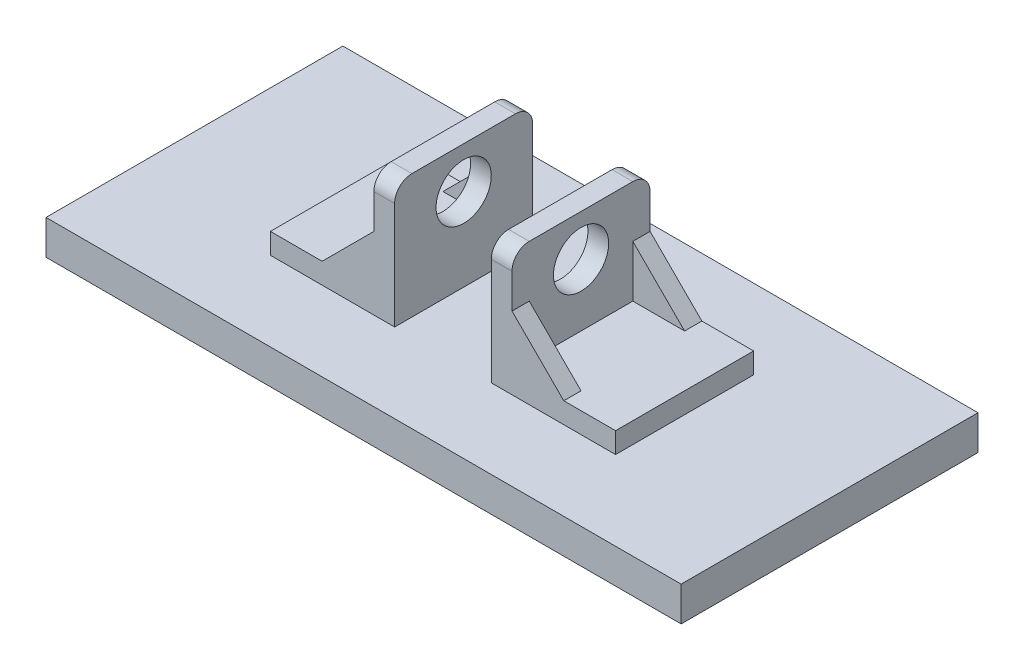
SolidWorks part; units mm, degrees
ref_plane "Front Plane" through (0, 0, 0) normal (0, 0, 1) x (1, 0, 0)
ref_plane "Top Plane" through (0, 0, 0) normal (0, 1, 0) x (1, 0, 0)
ref_plane "Right Plane" through (0, 0, 0) normal (1, 0, 0) x (0, 0, -1)
sketch "Sketch1" plane through (0, 0, 0) normal (0, 1, 0) x (1, 0, 0)
  line L1 (92, 43) -> (-92, 43)
  line L2 (92, 43) -> (92, -43)
  line L3 (92, -43) -> (-92, -43)
  line L4 (-92, 43) -> (-92, -43)
  line L5 (92, 43) -> (-92, -43) construction
  line L6 (92, -43) -> (-92, 43) construction
  point P0 (0, 0)
  dimension "D1" = 184
  dimension "D2" = 86
extrude "plate" add sketch "Sketch1" along normal blind 10
sketch "Sketch2" plane through (0, 0, 0) normal (0, 0, 1) x (1, 0, 0)
  line L0 (-14, 10) -> (-14, 46)
  line L1 (-92, 10) -> (92, 10) construction
  line L2 (-14, 46) -> (-20, 46)
  line L3 (-20, 46) -> (-20, 16)
  line L4 (-20, 16) -> (-50, 16)
  line L5 (-50, 16) -> (-50, 10)
  line L6 (-50, 10) -> (-14, 10)
  line L7 (-20, 31) -> (-35, 16)
  line L8 (0, 0) -> (0, 10) construction
  line L9 (20, 31) -> (35, 16)
  line L10 (50, 16) -> (50, 10)
  line L11 (20, 16) -> (50, 16)
  line L12 (20, 46) -> (20, 16)
  line L13 (14, 46) -> (20, 46)
  line L14 (14, 10) -> (14, 46)
  line L15 (50, 10) -> (14, 10)
  dimension "D1" = 45
  dimension "D2" = 6
  dimension "D3" = 14
  dimension "D4" = 36
  dimension "D5" = 15
extrude "Boss-Extrude1" add sketch "Sketch2" along normal mid plane 40 contours L0 L2 L3 L4 L5 L6 | L10 L15 L14 L13 L12 L11
extrude "Boss-Extrude2" add sketch "Sketch2<3>" along normal blind 5 from offset 15 contours L3 L7 L4 | L9 L12 L11 region at (-25, 21, 0) region at (25, 21, 0)
sketch "Sketch2<3>" plane through (0, 0, 0) normal (0, 0, 1) x (1, 0, 0) same geometry as "Sketch2"
extrude "Boss-Extrude3" add sketch "Sketch2<4>" against normal blind 5 from offset 15 contours L3 L7 L4 | L9 L12 L11 region at (-25, 21, 0) region at (25, 21, 0) offset against normal yes
sketch "Sketch2<4>" plane through (0, 0, 0) normal (0, 0, 1) x (1, 0, 0) same geometry as "Sketch2"
sketch "Sketch3" plane through (-20, 0, 0) normal (-1, 0, 0) x (0, 0, 1)
  line L0 (20, 46) -> (-20, 46) construction
  circle A0 centre (0, 34) radius 8
  dimension "D2" = 16
  dimension "D1" = 12
extrude "Cut-Extrude1" cut sketch "Sketch3" against normal up to surface (40 mm away) up to face at (20, 31, 0)
fillet "Fillet1" radius 5 4 edges at (-17, 46, -20) (17, 46, 20) (17, 46, -20) (-17, 46, 20)
equation "\"D1@Sketch1\"=144+40"
equation "\"D2@Sketch1\"=46+40"
